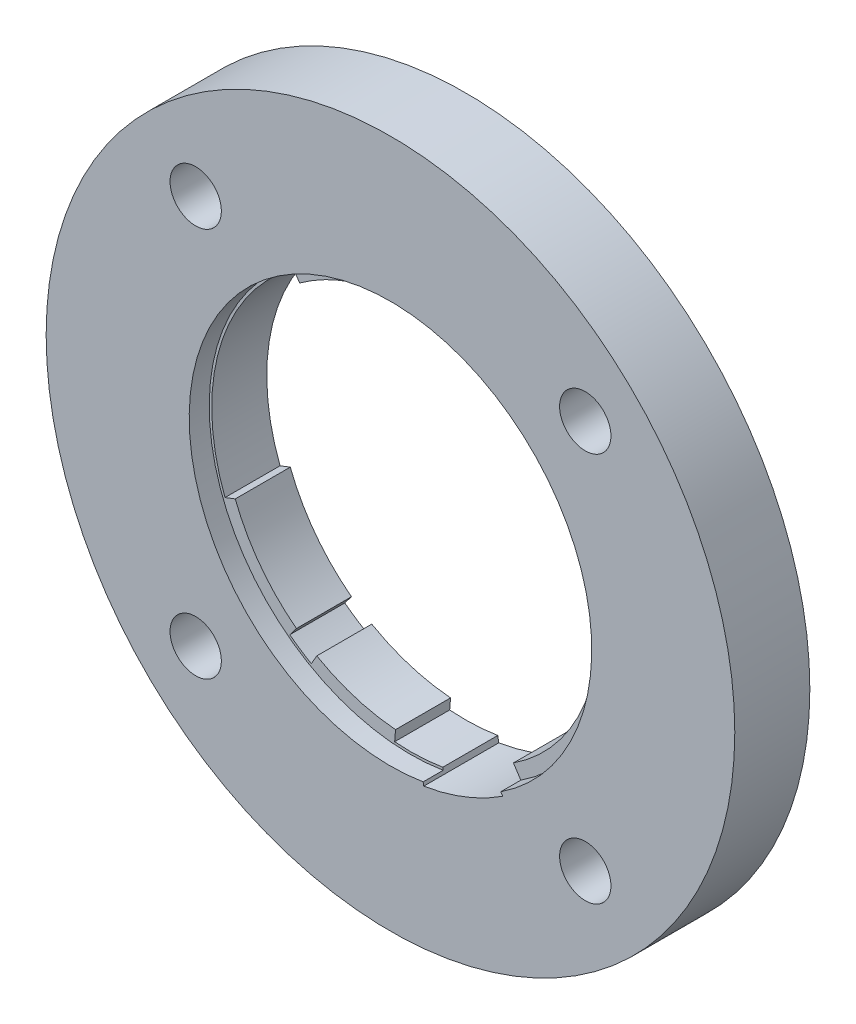
SolidWorks part; units mm, degrees
ref_plane "Front Plane" through (0, 0, 0) normal (0, 0, 1) x (1, 0, 0)
ref_plane "Top Plane" through (0, 0, 0) normal (0, 1, 0) x (1, 0, 0)
ref_plane "Right Plane" through (0, 0, 0) normal (1, 0, 0) x (0, 0, -1)
ref_axis "Z" through (0, 0, -0.1647) along (0, 0, 1)
sketch "Sketch1" plane through (0, 0, 0) normal (0, 1, 0) x (1, 0, 0)
  line L0 (-15.875, 0) -> (-27.5, 0)
  line L1 (-27.5, 0) -> (-27.5, -5.994)
  line L2 (-27.5, -5.994) -> (-16.075, -5.994)
  line L3 (-16.075, -5.994) -> (-16.075, -4.394)
  line L4 (-16.075, -4.394) -> (-15.875, -4.394)
  line L5 (-15.875, -4.394) -> (-15.875, 0)
  line L6 (0, -1.0245) -> (0, 4.9373) construction
  dimension "D1" = 1.6
  dimension "D2" = 32.15
  dimension "D3" = 31.75
  dimension "D4" = 4.394
  dimension "D5" = 55
revolve "Revolve1" add sketch "Sketch1" angle 360 about L6
sketch "Sketch2" plane through (0, 0, 0) normal (0, 0, 1) x (1, 0, 0)
  line L0 (-15.5563, 15.5563) -> (0, 0) construction
  line L1 (0, 0) -> (0, 34.6787) construction
  circle A0 centre (-15.5563, 15.5563) radius 2.05
  circle A1 centre (15.5563, 15.5563) radius 2.05
  circle A2 centre (15.5563, -15.5563) radius 2.05
  circle A3 centre (-15.5563, -15.5563) radius 2.05
  point P13 (0, 0)
  dimension "D4" = 4.1
  dimension "D1" = 22
  dimension "D3" = 45
  dimension "D2" = 4
extrude "Cut-Extrude1" cut sketch "Sketch2" along normal through all
sketch "Sketch3" plane through (0, 0, 0) normal (0, 0, -1) x (-1, 0, 0)
  line L4 (7.4875, -12.9976) -> (9.2451, -16.0487)
  line L5 (1.1963, -14.9522) -> (1.4772, -18.4621)
  line L6 (-7.1892, -13.1649) -> (-8.8768, -16.2553)
  line L7 (-10.0559, 11.1301) -> (-12.4165, 13.7427)
  line L13 (9.1107, -11.9162) -> (11.0541, -14.4581)
  line L14 (13.9968, -5.3934) -> (16.9826, -6.5439)
  line L15 (2.1331, 14.8476) -> (2.9428, 20.4836)
  line L16 (8.8468, 12.1134) -> (12.205, 16.7116)
  line L17 (7.4875, -12.9976) -> (9.2451, -16.0487)
  line L18 (1.1963, -14.9522) -> (1.4772, -18.4621)
  arc A0 (7.4875, -12.9976) -> (1.1963, -14.9522) centre (0, 0) cw
  arc A1 (9.2451, -16.0487) -> (1.4772, -18.4621) centre (0, 0) cw
  circle A2 centre (0, 0) radius 15.875 construction
  arc A3 (-7.1892, -13.1649) -> (-10.0559, 11.1301) centre (0, 0) cw
  arc A4 (-8.8768, -16.2553) -> (-12.4165, 13.7427) centre (0, 0) cw
  arc A9 (9.1107, -11.9162) -> (13.9968, -5.3934) centre (0, 0) ccw
  arc A10 (11.0541, -14.4581) -> (16.9826, -6.5439) centre (0, 0) ccw
  arc A11 (2.9428, 20.4836) -> (12.205, 16.7116) centre (0, 0) cw
  arc A12 (2.1331, 14.8476) -> (8.8468, 12.1134) centre (0, 0) cw
  arc A13 (9.2451, -16.0487) -> (1.4772, -18.4621) centre (0, 0) cw
  arc A14 (7.4875, -12.9976) -> (1.1963, -14.9522) centre (0, 0) cw
  point P22 (0, 0)
  point P23 (3.4812, 13.7448)
  point P24 (8.8111, 12.0646)
  point P25 (2.0704, 14.4108)
  point P26 (0, 0)
  point P38 (0, 0)
  point P39 (0, 0)
  circle M23 centre (0, 0) radius 15.875
  dimension "D1" = 15
  dimension "D2" = 15
  dimension "D3" = 15
  dimension "D4" = 15
extrude "Boss-Extrude2" add sketch "Sketch3" against normal up to surface (4.394 mm away) contours L6 A3 L7 M23 | L4 A0 L5 M23 | A9 L13 L14 M23 | L15 A12 L16 M23 region at (-4.5442, -14.6261, 0) region at (-12.2034, -9.1414, 0) region at (15.4961, -1.8285, 0) region at (-5.7665, 14.1596, 0) up to face at (15.875, 0, 4.394)
sketch "Sketch4" plane through (0, 0, 0) normal (0, 0, -1) x (-1, 0, 0)
  line L0 (-8.963, -13.6806) -> (0, 0)
  line L5 (0, 0) -> (-2.6558, -16.1382)
  arc A0 (-8.963, -13.6806) -> (-2.6558, -16.1382) centre (0, 0) ccw
extrude "Cut-Extrude2" cut sketch "Sketch4" against normal through all both and the other way through all
